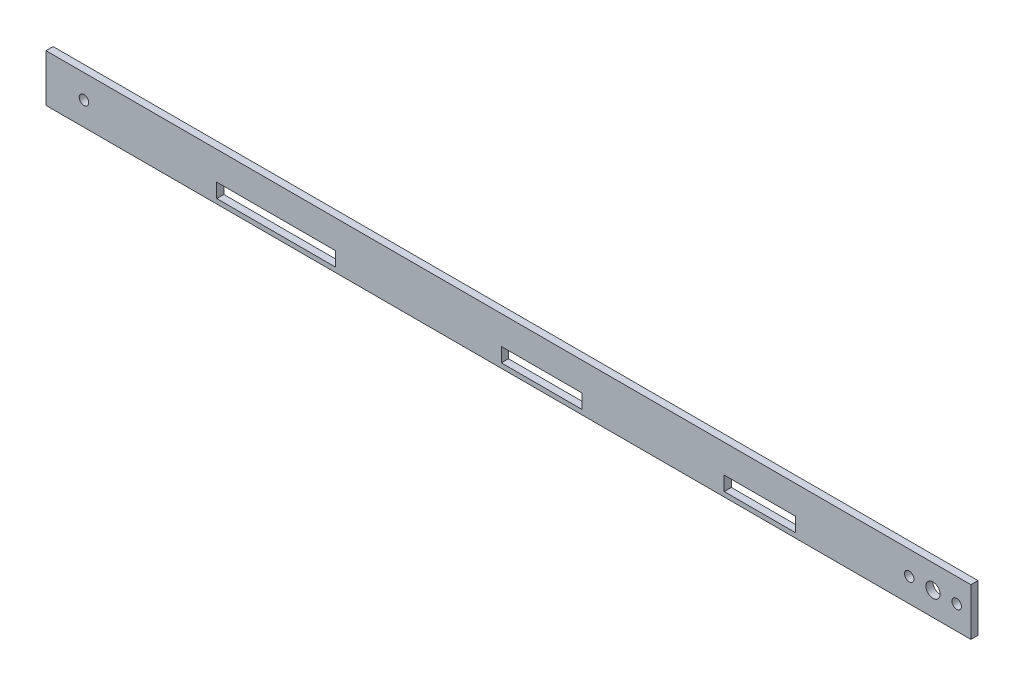
SolidWorks part; units mm, degrees
ref_plane "前视基准面" through (0, 0, 0) normal (0, 0, 1) x (1, 0, 0)
ref_plane "上视基准面" through (0, 0, 0) normal (0, 1, 0) x (1, 0, 0)
ref_plane "右视基准面" through (0, 0, 0) normal (1, 0, 0) x (0, 0, -1)
sketch "草图1" plane through (0, 0, 0) normal (0, 0, 1) x (1, 0, 0)
  line L1 (-200, 0) -> (-5, 0)
  line L2 (-200, 0) -> (-200, -10)
  line L3 (-200, -10) -> (-5, -10)
  line L4 (-5, 0) -> (-5, -10)
  dimension "D1" = 195
  dimension "D2" = 10
extrude "凸台-拉伸1" add sketch "草图1" along normal blind 1.5
sketch "草图2" plane through (0, 0, 1.5) normal (0, 0, 1) x (1, 0, 0)
  line L0 (-200, -5) -> (-192, -5)
  line L1 (-200, 0) -> (-200, -10) construction
  circle A0 centre (-192, -5) radius 1
  dimension "D2" = 2
  dimension "D1" = 8
extrude "切除-拉伸1" cut sketch "草图2" against normal blind 15 and the other way blind 12 contours A0 region at (-192, -5.9717, 1.5)
ref_plane "基准面1" through (-102.5, 0, 0) normal (-1, 0, 0) x (0, 0, 1)
sketch "草图3" plane through (0, 0, 1.5) normal (0, 0, 1) x (1, 0, 0)
  line L1 (-5, -10) -> (-5, 0) construction
  circle A1 centre (-13, -5) radius 1.5
  circle A2 centre (-8, -5) radius 1
  circle A3 centre (-18, -5) radius 1
  dimension "D1" = 5
  dimension "D2" = 3
  dimension "D3" = 2
  dimension "D4" = 8
  dimension "D5" = 5
extrude "切除-拉伸2" cut sketch "草图3" against normal blind 31 and the other way blind 32 contours A1 | A2 | A3 region at (-13, -5, 1.5)
sketch "草图4" plane through (0, 0, 0) normal (0, 0, -1) x (-1, 0, 0)
  line L0 (200, -10) -> (5, -10) construction
  line L2 (22, -10) -> (22, -6)
  line L3 (57, -6) -> (164, -6)
  line L4 (164, -9) -> (164, -6)
  line L5 (22, -6) -> (57, -6)
  line L6 (164, -6) -> (164, -9)
  line L7 (200, 0) -> (200, -10) construction
  line L8 (42, -6) -> (42, -9)
  line L9 (164, -6) -> (139, -6)
  line L10 (164, -6) -> (164, -9)
  line L12 (139, -6) -> (139, -9.9986)
  line L16 (22, -6) -> (22, -10)
  line L18 (57, -6) -> (57, -10)
  line L21 (104, -6) -> (87, -6)
  line L22 (104, -6) -> (104, -9)
  line L23 (104, -9) -> (87, -9)
  line L24 (87, -6) -> (87, -9)
  line L31 (200, -10) -> (5, -10) construction
  line L32 (22, -9) -> (164, -9)
  point P4 (93.0123, -8.0006)
  point P11 (157.5, -8.0002)
  point P14 (29.5, -8.0009)
  point P19 (97.1324, -7.5)
  dimension "D1" = 142
  dimension "D2" = 4
  dimension "D3" = 36
  dimension "D4" = 25
  dimension "D5" = 17
  dimension "D6" = 15
  dimension "D8" = 3
  dimension "D9" = 30
  dimension "D10" = 35
ref_plane "基准面2" through (-200, -10, 0) normal (1, 0, 0) x (0, 0, -1)
extrude "切除-拉伸3" cut sketch "草图4" against normal blind 10 contours L3 L24 L23 L22 | L12 L32 L4 L3 | L8 L32 L18 L5 region at (-49.5, -7.5, 0) region at (-95.5, -7.5, 0) region at (-151.5, -7.5, 0)
